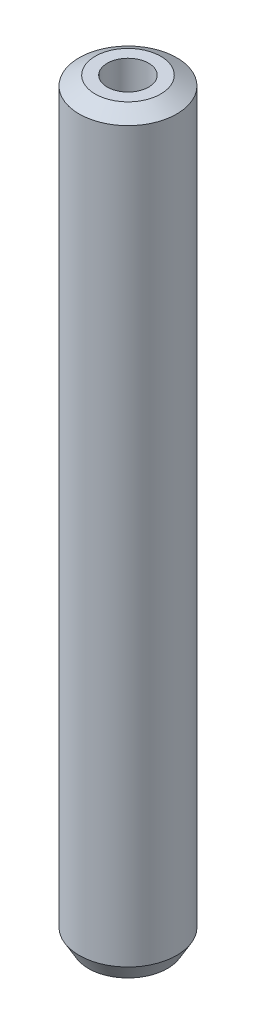
SolidWorks part; units mm, degrees
ref_plane "Front Plane" through (0, 0, 0) normal (0, 0, 1) x (1, 0, 0)
ref_plane "Top Plane" through (0, 0, 0) normal (0, 1, 0) x (1, 0, 0)
ref_plane "Right Plane" through (0, 0, 0) normal (1, 0, 0) x (0, 0, -1)
sketch "Sketch1" plane through (0, 0, 0) normal (0, 1, 0) x (1, 0, 0)
  circle A0 centre (0, 0) radius 15
  dimension "SHAFT_OD" = 30
extrude "Boss-Extrude1" add sketch "Sketch1" along normal blind 231.7604
sketch "Sketch2" plane through (0, 0, 0) normal (0, 1, 0) x (1, 0, 0)
  circle A0 centre (0, 0) radius 6.3678
  dimension "BORE_D" = 12.7356
extrude "Cut-Extrude1" cut sketch "Sketch2" along normal through all
chamfer "Chamfer1" distance 2.8484 angle 60 2 edges at (0, 231.7604, 15) (0, 0, 15) first distance on face at (0, 231.7604, 15) first distance on face at (0, 0, 6.3678)
